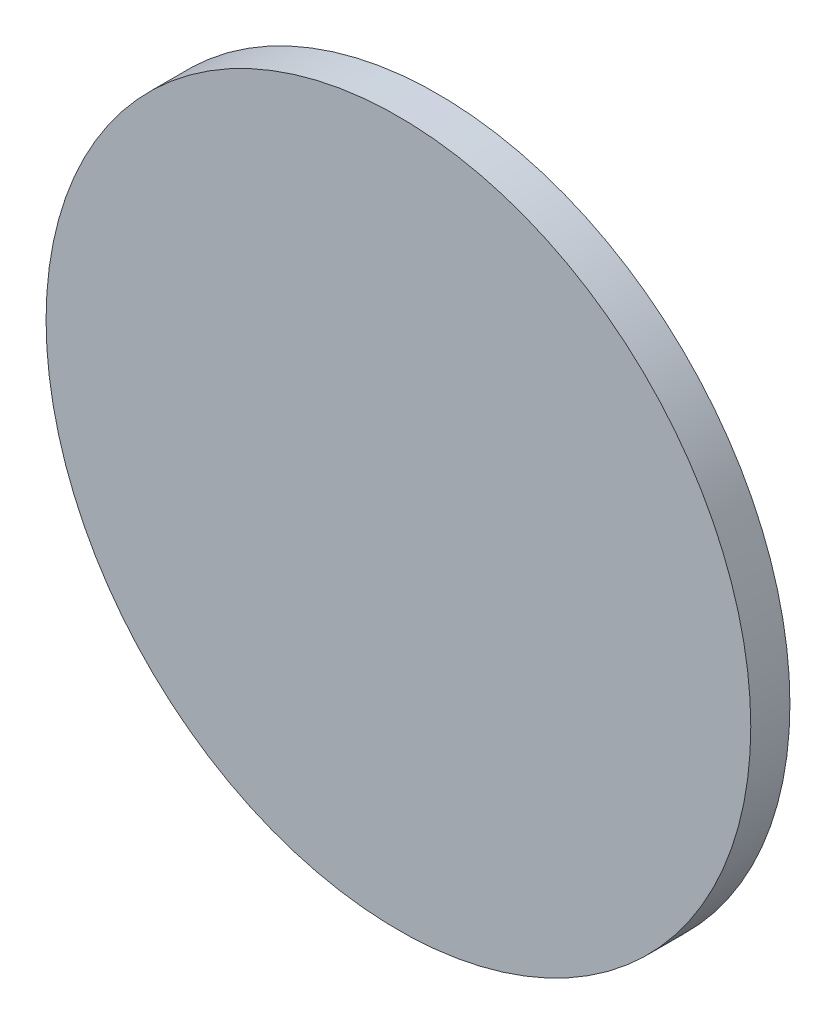
SolidWorks part; units mm, degrees
ref_plane "Front" through (0, 0, 0) normal (0, 0, 1) x (1, 0, 0)
ref_plane "Top" through (0, 0, 0) normal (0, 1, 0) x (1, 0, 0)
ref_plane "Right" through (0, 0, 0) normal (1, 0, 0) x (0, 0, -1)
other "Configuration Table"
sketch "Sketch1" plane through (0, 0, 0) normal (0, 0, 1) x (1, 0, 0)
  circle A0 centre (0, 0) radius 228.6
  dimension "D1" = 457.2
extrude "Extrude1" add sketch "Sketch1" against normal blind 25.4
ref_axis "Axis1" through (0, 0, 244.6289) along (0, 0, -1)
